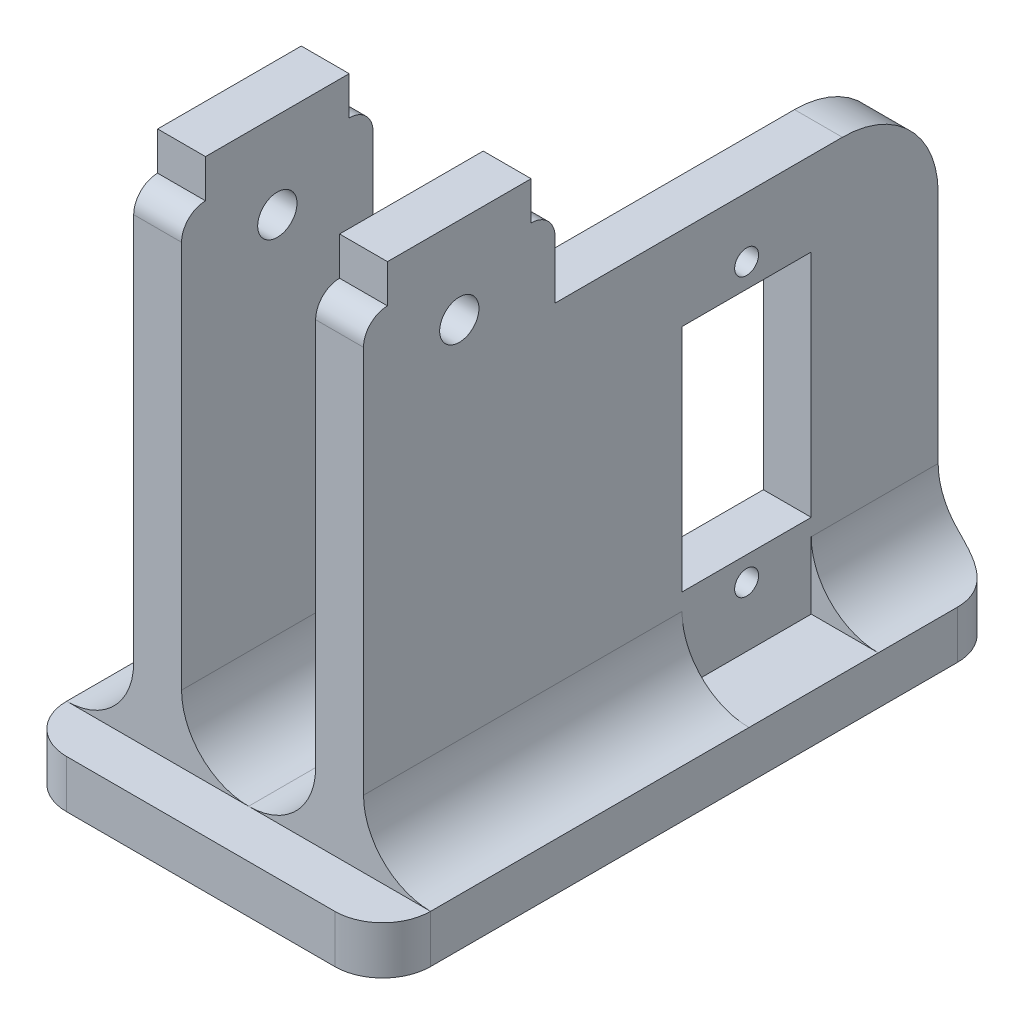
SolidWorks part; units mm, degrees
ref_plane "Front Plane" through (0, 0, 0) normal (0, 0, 1) x (1, 0, 0)
ref_plane "Top Plane" through (0, 0, 0) normal (0, 1, 0) x (1, 0, 0)
ref_plane "Right Plane" through (0, 0, 0) normal (1, 0, 0) x (0, 0, -1)
sketch "Sketch1" plane through (0, 0, 0) normal (0, 1, 0) x (1, 0, 0)
  line L1 (4.5, 32.5) -> (-4.5, 32.5)
  line L2 (9.5, 27.5) -> (9.5, -27.5)
  line L3 (4.5, -32.5) -> (-9.5, -32.5)
  line L4 (-9.5, 27.5) -> (-9.5, 2.5)
  line L5 (9.5, 32.5) -> (-9.5, -32.5) construction
  line L6 (9.5, -32.5) -> (-9.5, 32.5) construction
  line L7 (-9.5, -32.5) -> (-23.5, -32.5)
  line L8 (-9.5, -32.5) -> (-9.5, -28.75)
  line L9 (-14.5, -2.5) -> (-23.5, -2.5)
  line L10 (-28.5, -27.5) -> (-28.5, -7.5)
  line L17 (-9.5, -28.75) -> (-9.5, -32.5) construction
  line L18 (-9.5, -28.75) -> (-9.5, -32.5)
  line L19 (-9.5, -28.75) -> (-9.5, -32.5) construction
  line L20 (-9.5, -2.5) -> (-9.5, -32.5) construction
  circle A0 centre (-9.5, -17.5) radius 1.5
  circle A1 centre (-9.5, -17.5) radius 11.25
  arc A2 (-14.5, -2.5) -> (-9.5, 2.5) centre (-14.5, 2.5) ccw
  arc A3 (-9.5, 27.5) -> (-4.5, 32.5) centre (-4.5, 27.5) cw
  arc A4 (9.5, 27.5) -> (4.5, 32.5) centre (4.5, 27.5) ccw
  arc A5 (9.5, -27.5) -> (4.5, -32.5) centre (4.5, -27.5) cw
  arc A6 (-23.5, -32.5) -> (-28.5, -27.5) centre (-23.5, -27.5) cw
  arc A7 (-23.5, -2.5) -> (-28.5, -7.5) centre (-23.5, -7.5) ccw
  point P0 (0, 0)
  point P1 (-9.5, -14.8744)
  point P7 (-9.5, -14.8744)
  point P29 (-28.5, -32.5)
  point P32 (-28.5, -2.5)
  dimension "D4" = 3
  dimension "D5" = 22.5
  dimension "D7" = 5
  dimension "D1" = 65
  dimension "D2" = 38
  dimension "D3" = 19
  dimension "D6" = 30
extrude "Boss-Extrude1" add sketch "Sketch1" along normal blind 5 contours L9 A7 L10 A6 L7 A1 L3 A5 L2 A4 L1 A3 L4 A2 | A1 A0 region at (-17.23, 0, 9.77) region at (-4.9503, 0, 2.1681)
extrude "Cut-Extrude1" cut sketch "Sketch1<3>" along normal blind 2 contours A1 A0 region at (-17.23, 0, 9.77)
sketch "Sketch1<3>" plane through (0, 0, 0) normal (0, 1, 0) x (1, 0, 0) same geometry as "Sketch1"
ref_plane "Plane1" through (-9.5, 0, 0) normal (1, 0, 0) x (0, 0, -1)
ref_plane "Plane2" through (-2.5, 0, 0) normal (1, 0, 0) x (0, 0, -1)
sketch "Sketch2" plane through (-2.5, 0, 0) normal (1, 0, 0) x (0, 0, -1)
  line L0 (32.5, 5) -> (32.5, 36.5)
  line L1 (22.5, 46.5) -> (-7.5, 46.5)
  line L2 (-7.5, 46.5) -> (-7.5, 52.5)
  line L3 (-10, 55) -> (-10, 59)
  line L4 (-10, 59) -> (-25, 59)
  line L5 (-25, 59) -> (-25, 55)
  line L6 (-27.5, 52.5) -> (-27.5, 5)
  line L7 (-27.5, 5) -> (32.5, 5)
  line L8 (-32.5, 5) -> (-32.5, 0) construction
  line L9 (-2.5, 5) -> (-2.5, 0) construction
  line L10 (-32.5, 0) -> (-27.5, 0) construction
  line L11 (-17.5, 59) -> (-17.5, 50) construction
  line L12 (-7.5, 25.75) -> (32.5, 25.75) construction
  line L13 (19.25, 37.75) -> (5.75, 37.75)
  line L14 (19.25, 37.75) -> (19.25, 13.75)
  line L15 (19.25, 13.75) -> (5.75, 13.75)
  line L16 (5.75, 37.75) -> (5.75, 13.75)
  line L17 (19.25, 37.75) -> (5.75, 13.75) construction
  line L18 (19.25, 13.75) -> (5.75, 37.75) construction
  line L19 (12.5, 46.5) -> (12.5, 5) construction
  arc A0 (-7.5, 52.5) -> (-10, 55) centre (-10, 52.5) ccw
  arc A1 (-25, 55) -> (-27.5, 52.5) centre (-25, 52.5) ccw
  circle A2 centre (-17.5, 50) radius 2.05
  arc A3 (32.5, 36.5) -> (22.5, 46.5) centre (22.5, 36.5) ccw
  circle A4 centre (12.5, 40.25) radius 1.25
  circle A5 centre (12.5, 11.25) radius 1.25
  point P20 (12.5, 25.75)
  dimension "D5" = 2.5
  dimension "D6" = 2.5
  dimension "D7" = 4.1
  dimension "D8" = 9
  dimension "D12" = 10
  dimension "D14" = 2.5
  dimension "D1" = 5
  dimension "D2" = 5
  dimension "D3" = 59
  dimension "D4" = 4
  dimension "D9" = 13.5
  dimension "D10" = 24
  dimension "D11" = 6
  dimension "D13" = 40
  dimension "D15" = 2.5
  dimension "D16" = 2.5
extrude "Boss-Extrude2" add sketch "Sketch2" along normal blind 5
fillet "Fillet1" radius 7 2 edges at (2.5, 5, -2.5) (-2.5, 5, -2.5)
sketch "Sketch3" plane through (0, 13.75, 0) normal (0, 1, 0) x (1, 0, 0)
  line L0 (9.5, 27.5) -> (9.5, -27.5) construction
  line L1 (2.5, 19.25) -> (9.5, 19.25)
  line L2 (2.5, 19.25) -> (2.5, 5.75)
  line L3 (2.5, 5.75) -> (9.5, 5.75)
  line L4 (9.5, 19.25) -> (9.5, 5.75)
  line L5 (2.5, 22.5) -> (2.5, -7.5) construction
  line L6 (2.5, 5.75) -> (-2.5, 5.75) construction
  point P7 (2.5, 5.9372)
extrude "Cut-Extrude2" cut sketch "Sketch3" against normal up to vertex (8.75 mm away) up to point (9.5, 5, -27.5)
ref_plane "Plane3" through (-16.5, 0, 0) normal (1, 0, 0) x (0, 0, -1)
sketch "Sketch4" plane through (-16.5, 0, 0) normal (1, 0, 0) x (0, 0, -1)
  line L0 (-7.5, 46.5) -> (-7.5, 5)
  line L4 (19.25, 37.75) -> (5.75, 37.75)
  line L5 (5.75, 37.75) -> (5.75, 13.75)
  line L6 (5.75, 13.75) -> (19.25, 13.75)
  line L7 (19.25, 13.75) -> (19.25, 37.75)
  line L8 (19.25, 37.75) -> (5.75, 37.75)
  line L9 (5.75, 37.75) -> (5.75, 13.75)
  line L10 (5.75, 13.75) -> (19.25, 13.75)
  line L11 (19.25, 13.75) -> (19.25, 37.75)
  line L16 (32.5, 5) -> (32.5, 36.5)
  line L17 (-27.5, 5) -> (32.5, 5)
  line L18 (-27.5, 52.5) -> (-27.5, 5)
  line L19 (-25, 59) -> (-25, 55)
  line L20 (-10, 59) -> (-25, 59)
  line L21 (-10, 55) -> (-10, 59)
  line L22 (-7.5, 46.5) -> (-7.5, 52.5)
  line L23 (22.5, 46.5) -> (-7.5, 46.5)
  line L24 (32.5, 5) -> (32.5, 36.5)
  line L25 (-27.5, 5) -> (32.5, 5)
  line L26 (-27.5, 52.5) -> (-27.5, 5)
  line L27 (-25, 59) -> (-25, 55)
  line L28 (-10, 59) -> (-25, 59)
  line L29 (-10, 55) -> (-10, 59)
  line L30 (-7.5, 46.5) -> (-7.5, 52.5)
  line L31 (22.5, 46.5) -> (-7.5, 46.5)
  circle A1 centre (-17.5, 50) radius 2.05
  circle A2 centre (-17.5, 50) radius 2.05
  circle A3 centre (12.5, 11.25) radius 1.25
  circle A4 centre (12.5, 11.25) radius 1.25
  arc A5 (-25, 55) -> (-27.5, 52.5) centre (-25, 52.5) ccw
  arc A6 (-7.5, 52.5) -> (-10, 55) centre (-10, 52.5) ccw
  arc A7 (32.5, 36.5) -> (22.5, 46.5) centre (22.5, 36.5) ccw
  arc A8 (-25, 55) -> (-27.5, 52.5) centre (-25, 52.5) ccw
  arc A9 (-7.5, 52.5) -> (-10, 55) centre (-10, 52.5) ccw
  arc A10 (32.5, 36.5) -> (22.5, 46.5) centre (22.5, 36.5) ccw
  circle A11 centre (12.5, 40.25) radius 1.25
  circle A12 centre (12.5, 40.25) radius 1.25
  dimension "D1" = 0
  dimension "D2" = 0
  dimension "D3" = 0
  dimension "D4" = 0
  dimension "D5" = 0
extrude "Boss-Extrude3" add sketch "Sketch4" against normal blind 5 contours L30 A9 L29 L28 L27 A8 L26 L25 L0 A2 region at (-16.5, 31.2359, 17.5)
fillet "Fillet2" radius 7 2 edges at (-16.5, 5, 17.5) (-21.5, 5, 17.5)
